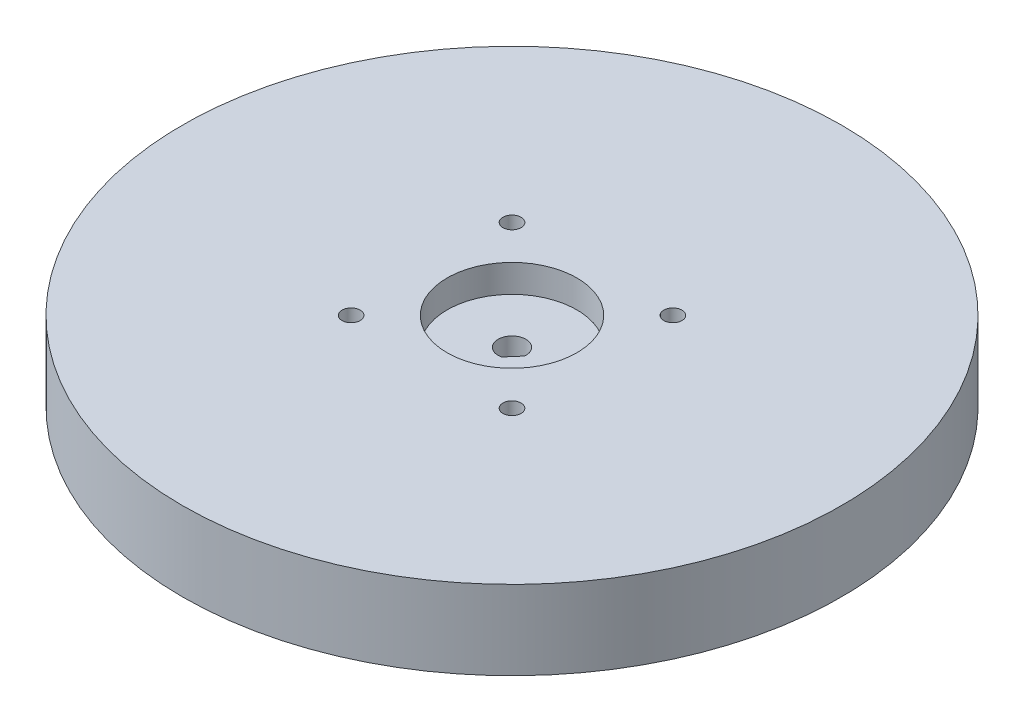
SolidWorks part; units mm, degrees
ref_plane "Front Plane" through (0, 0, 0) normal (0, 0, 1) x (1, 0, 0)
ref_plane "Top Plane" through (0, 0, 0) normal (0, 1, 0) x (1, 0, 0)
ref_plane "Right Plane" through (0, 0, 0) normal (1, 0, 0) x (0, 0, -1)
sketch "Sketch2" plane through (0, 0, 0) normal (0, 1, 0) x (1, 0, 0)
  circle A1 centre (0, 0) radius 63.5
  dimension "D1" = 127
extrude "Boss-Extrude1" add sketch "Sketch2" along normal blind 15.24 contours A1 | A1 | A1 | A1 | A1 | A1 | A1 | A1 | A1 | A1 | A1 | A1 | A1 | A1 | A1 | A1 | A1 | A1 | A1 | A1 | A1 | A1 | A1 | A1 | A1 | A1 | A1 | A1 | A1 | A1 | A1 | A1 | A1 | A1 | A1 | A1 | A1 | A1 | A1 | A1 | A1 | A1 | A1 | A1 | A1 | A1 region at (0, 0, 0)
sketch "Sketch3" plane through (0, 15.24, 0) normal (0, 1, 0) x (1, 0, 0)
  line L0 (0.6187, -2.6108) -> (2.6708, -0.2566)
  circle A5 centre (0, 0) radius 2.6831
  point P0 (0, 0)
  dimension "D1" = 5.3662
extrude "Cut-Extrude3" cut sketch "Sketch3" against normal through all contours L0 A5 region at (-0.0888, 15.24, -0.0774)
sketch "Sketch4" plane through (0, 15.24, 0) normal (0, 1, 0) x (1, 0, 0)
  line L0 (-15.5, -15.5) -> (15.5, 15.5) construction
  circle A0 centre (-15.5, 15.5) radius 1.75
  circle A1 centre (15.5, 15.5) radius 1.75
  circle A2 centre (15.5, -15.5) radius 1.75
  circle A3 centre (-15.5, -15.5) radius 1.75
  point P8 (0, 0)
  dimension "D1" = 3.5
  dimension "D5" = 31
  dimension "D6" = 31
extrude "Cut-Extrude4" cut sketch "Sketch4" against normal blind 55.626
sketch "Sketch5" plane through (0, 15.24, 0) normal (0, 1, 0) x (1, 0, 0)
  circle A0 centre (0, 0) radius 12.5
  dimension "D1" = 25
extrude "Cut-Extrude5" cut sketch "Sketch5" against normal blind 5.334
